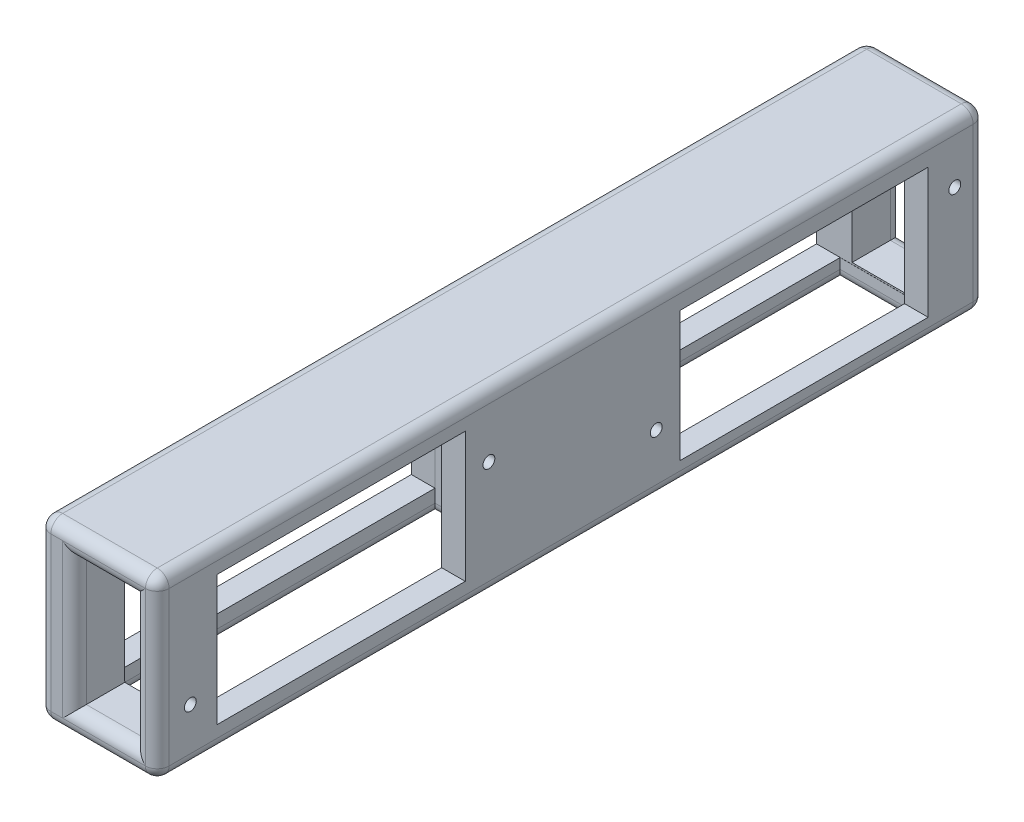
SolidWorks part; units mm, degrees
ref_plane "Plan de face" through (0, 0, 0) normal (0, 0, 1) x (1, 0, 0)
ref_plane "Plan de dessus" through (0, 0, 0) normal (0, 1, 0) x (1, 0, 0)
ref_plane "Plan de droite" through (0, 0, 0) normal (1, 0, 0) x (0, 0, -1)
sketch "Esquisse1" plane through (0, 0, 0) normal (1, 0, 0) x (0, 0, -1)
  line L1 (-67.0674, 25.7923) -> (72.9326, 25.7923)
  line L2 (-67.0674, 25.7923) -> (-67.0674, -4.2077)
  line L3 (-67.0674, -4.2077) -> (72.9326, -4.2077)
  line L4 (72.9326, 25.7923) -> (72.9326, -4.2077)
  dimension "D1" = 140
  dimension "D2" = 30
extrude "Boss.-Extru.1" add sketch "Esquisse1" along normal blind 20
sketch "Esquisse2" plane through (20, 0, 0) normal (1, 0, 0) x (0, 0, -1)
  line L1 (63.3326, -0.6811) -> (21.3326, -0.6811)
  line L2 (21.3326, -0.6811) -> (21.3326, 21.3189)
  line L3 (21.3326, 21.3189) -> (63.3326, 21.3189)
  line L4 (63.3326, -0.6811) -> (63.3326, 8.0689)
  line L5 (63.3326, 12.3189) -> (63.3326, 8.0689)
  line L8 (-0.5557, 12.4688) -> (70.2097, 12.4688) construction
  line L12 (63.3326, 21.3189) -> (63.3326, 12.3189)
  line L14 (72.9326, -4.2077) -> (72.9326, 25.7923) construction
  circle A0 centre (67.8326, 16.1189) radius 1
  circle A1 centre (17.3326, 5.8189) radius 1
  dimension "D5" = 2
  dimension "D7" = 2
  dimension "D1" = 22
  dimension "D2" = 4.5
  dimension "D3" = 42
  dimension "D6" = 6.5
  dimension "D8" = 4
  dimension "D9" = 5.2
  dimension "D12" = 5.1
  dimension "D13" = 8.75
extrude "Enlèv. mat.-Extru.1" cut sketch "Esquisse2" against normal blind 10
sketch "Esquisse4" plane through (20, 26.613, 128.3299) normal (1, 0, 0) x (0, 0, 1)
  line L0 (-113.3567, 26.8206) -> (-113.3567, 4.8206)
  line L1 (-113.3567, 4.8206) -> (-71.3567, 4.8206)
  line L3 (-71.3567, 26.8206) -> (-113.3567, 26.8206)
  line L6 (-71.3567, 13.5706) -> (-71.3567, 18.0706)
  line L7 (-132.5819, 12.4906) -> (-63.0974, 12.4906) construction
  line L11 (-71.3567, 4.8206) -> (-71.3567, 13.5706)
  line L12 (-71.3567, 18.0706) -> (-71.3567, 26.8206)
  circle A0 centre (-117.3567, 11.3206) radius 1
  circle A1 centre (-66.8567, 21.6206) radius 1
  dimension "D5" = 2
  dimension "D7" = 2
  dimension "D1" = 7.67
  dimension "D2" = 22
  dimension "D3" = 8.75
  dimension "D4" = 42
  dimension "D6" = 4
  dimension "D8" = 4.5
  dimension "D9" = 5.2
  dimension "D10" = 6.5
extrude "Enlèv. mat.-Extru.2" cut sketch "Esquisse4" against normal blind 10
sketch "Esquisse5" plane through (0, 0, 67.0674) normal (0, 0, 1) x (1, 0, 0)
  line L0 (6, 21.7923) -> (6, -0.2077)
  line L1 (6, -0.2077) -> (16, -0.2077)
  line L2 (16, -0.2077) -> (16, 21.7923)
  line L3 (16, 21.7923) -> (6, 21.7923)
  line L4 (0, 25.7923) -> (0, -4.2077) construction
  line L5 (20, 25.7923) -> (20, -4.2077) construction
  line L6 (20, -4.2077) -> (0, -4.2077) construction
  line L7 (20, 25.7923) -> (0, 25.7923) construction
  dimension "D1" = 6
  dimension "D2" = 4
  dimension "D3" = 4
  dimension "D4" = 4
extrude "Enlèv. mat.-Extru.3" cut sketch "Esquisse5" against normal blind 63
sketch "Esquisse6" plane through (0, 0, -72.9326) normal (0, 0, -1) x (-1, 0, 0)
  line L0 (-16, 21.7923) -> (-16, -0.2077)
  line L1 (-16, -0.2077) -> (-6, -0.2077)
  line L2 (-6, -0.2077) -> (-6, 21.7923)
  line L3 (-6, 21.7923) -> (-16, 21.7923)
  line L4 (-20, -4.2077) -> (-20, 25.7923) construction
  line L5 (0, -4.2077) -> (0, 25.7923) construction
  line L6 (-20, 25.7923) -> (0, 25.7923) construction
  line L7 (-20, -4.2077) -> (0, -4.2077) construction
  dimension "D1" = 4
  dimension "D2" = 6
  dimension "D3" = 4
  dimension "D4" = 4
extrude "Enlèv. mat.-Extru.4" cut sketch "Esquisse6" against normal blind 63
sketch "Esquisse7" plane through (0, -4.2077, 0) normal (0, -1, 0) x (1, 0, 0)
  line L0 (4, -64.4326) -> (16, -64.4326)
  line L1 (16, -64.4326) -> (16, -9.9326)
  line L2 (16, -9.9326) -> (4, -9.9326)
  line L3 (4, -9.9326) -> (4, -64.4326)
  line L4 (0, 67.0674) -> (0, -72.9326) construction
  line L5 (20, 67.0674) -> (20, -72.9326) construction
  line L6 (20, -72.9326) -> (0, -72.9326) construction
  dimension "D1" = 4
  dimension "D2" = 4
  dimension "D3" = 8.5
  dimension "D4" = 54.5
extrude "Enlèv. mat.-Extru.5" cut sketch "Esquisse7" against normal up to surface (26 mm away) up to face at (11, 21.7923, -41.4326)
sketch "Esquisse8" plane through (0, -4.2077, 0) normal (0, -1, 0) x (-1, 0, 0)
  line L0 (-4, -4.0674) -> (-16, -4.0674)
  line L1 (-16, -4.0674) -> (-16, -58.5674)
  line L2 (-16, -58.5674) -> (-4, -58.5674)
  line L3 (-4, -58.5674) -> (-4, -4.0674)
  line L4 (-20, -67.0674) -> (0, -67.0674) construction
  line L5 (0, -67.0674) -> (0, 72.9326) construction
  line L6 (-20, -67.0674) -> (-20, 72.9326) construction
  dimension "D1" = 8.5
  dimension "D2" = 54.5
  dimension "D3" = 4
  dimension "D4" = 4
extrude "Enlèv. mat.-Extru.6" cut sketch "Esquisse8" against normal up to surface (26 mm away) up to face at (14.5, 21.7923, 35.7703)
fillet "Congé1" radius 2 28 edges at (20, 10.7923, 67.0674) (0, 10.7923, 67.0674) (11, -0.2077, 67.0674) (16, 10.7923, 67.0674) (11, 21.7923, 67.0674) (6, 10.7923, 67.0674) (20, 10.7923, -72.9326) (0, 10.7923, -72.9326) (11, -0.2077, -72.9326) (6, 10.7923, -72.9326) (11, 21.7923, -72.9326) (16, 10.7923, -72.9326) (10, -4.2077, 67.0674) (20, -4.2077, -2.9326) (10, -4.2077, -72.9326) (0, -4.2077, -2.9326) (16, -4.2077, -37.1826) (10, -4.2077, -9.9326) (10, -4.2077, -64.4326) (16, -4.2077, 31.3174) (10, -4.2077, 58.5674) (10, -4.2077, 4.0674) (10, 25.7923, -72.9326) (20, 25.7923, -2.9326) (10, 25.7923, 67.0674) (0, 25.7923, -2.9326) (4, -4.2077, 31.3174) (4, -4.2077, -37.1826)
sketch "Esquisse9" plane through (16, 0, 0) normal (-1, 0, 0) x (0, 0, 1)
  line L9 (58.6092, 21.7923) -> (4.0904, 21.7923)
  line L10 (58.6092, 21.7923) -> (58.6092, 0)
  line L11 (58.6092, 0) -> (4.0904, 0)
  line L12 (4.0904, 21.7923) -> (4.0904, 0)
extrude "Enlèv. mat.-Extru.7" cut sketch "Esquisse9" along normal through all
sketch "Esquisse11" plane through (16, 0, 0) normal (-1, 0, 0) x (0, 0, 1)
  line L9 (-9.9335, 21.3088) -> (-64.4523, 21.3088)
  line L10 (-9.9335, 21.3088) -> (-9.9335, -0.4835)
  line L11 (-9.9335, -0.4835) -> (-64.4523, -0.4835)
  line L12 (-64.4523, 21.3088) -> (-64.4523, -0.4835)
extrude "Enlèv. mat.-Extru.8" cut sketch "Esquisse11" along normal through all
